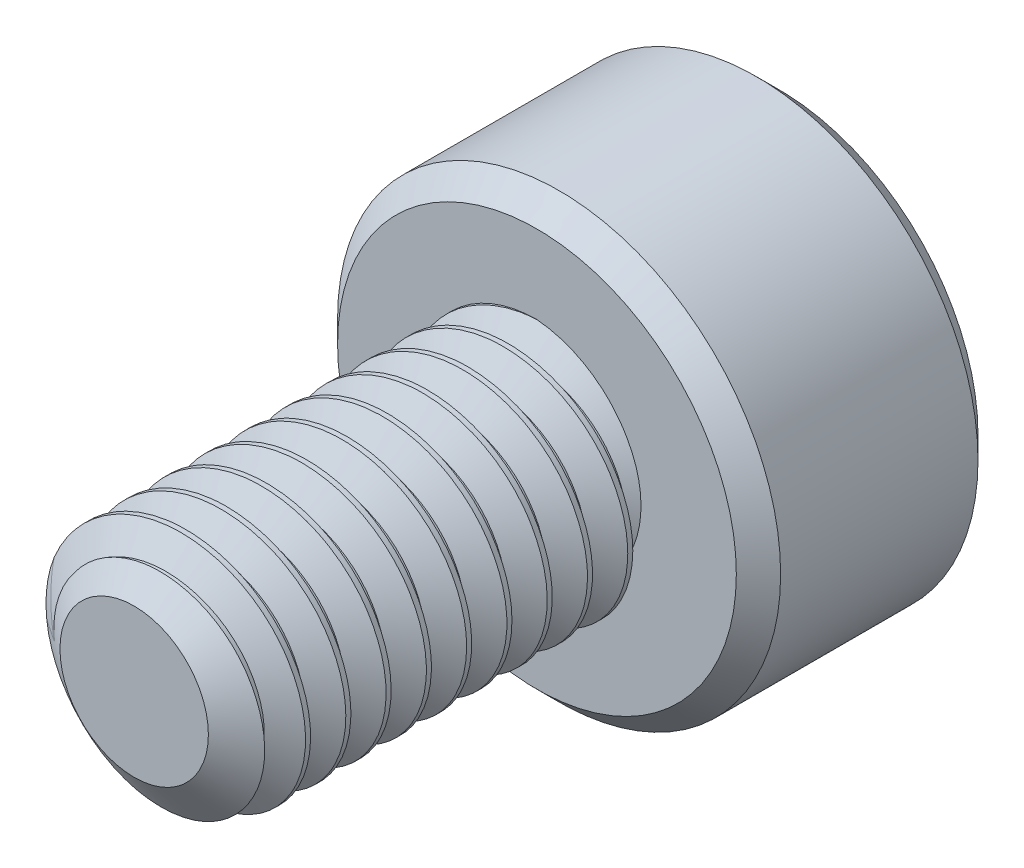
SolidWorks part; units mm, degrees
other "DetailItem1"
ref_plane "Front Plane" through (0, 0, 0) normal (0, 0, 1) x (1, 0, 0)
ref_plane "Top Plane" through (0, 0, 0) normal (0, 1, 0) x (1, 0, 0)
ref_plane "Right Plane" through (0, 0, 0) normal (1, 0, 0) x (0, 0, -1)
sketch "Sketch1" plane through (0, 0, 0) normal (0, 0, 1) x (1, 0, 0)
  circle A0 centre (0, 0) radius 1.5
  dimension "OD" = 3
extrude "Extrude1" add sketch "Sketch1" against normal blind 5
sketch "Sketch2" plane through (0, 0, 0) normal (0, 0, 1) x (1, 0, 0)
  circle A0 centre (0, 0) radius 1.5 construction
  circle A1 centre (0, 0) radius 1.5
curve "Helix/Spiral1" pitch 0.5 height 5.5 radius 1.5 centre (0, 0, 0) axis (0, 0, -1) start towards (0, 1, 0) parameters "pitch"=0.5
sketch "Sketch3" plane through (0, 0, 0) normal (1, 0, 0) x (0, 0, -1)
  line L0 (-0.4375, 1.5) -> (-0.25, 1.1752)
  line L1 (-0.25, 1.1752) -> (-0.1875, 1.1752)
  line L2 (-0.1875, 1.1752) -> (0, 1.5)
  line L3 (-0.4375, 1.5) -> (0, 1.5)
  line L4 (-0.2187, 1.5) -> (-0.2188, 1.1752) construction
  line L5 (-0.3438, 1.3376) -> (-0.0938, 1.3376) construction
  line L6 (0, 1.5) -> (0, -1.5) construction
  dimension "D1" = 0.0625
  dimension "D2" = 0.25
  dimension "D3" = 60
sweep "Cut-Sweep1" cut profiles "Sketch3" path "Helix/Spiral1"
sketch "Sketch4" plane through (0, 0, 0) normal (1, 0, 0) x (0, 0, -1)
  line L0 (0.4053, 1.5) -> (0, 0.9212)
  line L1 (0, 0.9212) -> (0, 1.5)
  line L2 (0.4053, 1.5) -> (0, 1.5)
  line L3 (-0.4375, 1.5) -> (0, 1.5) construction
  line L4 (0, 0) -> (7.0209, 0) construction
  dimension "D1" = 55
  dimension "D2" = 0.254
revolve "Cut-Revolve1" cut sketch "Sketch4" angle 360 about L4
sketch "Sketch6" plane through (0, 0, -5) normal (0, 0, -1) x (-1, 0, 0)
  circle A0 centre (0, 0) radius 2.75
  dimension "head dia" = 5.5
extrude "Extrude2" add sketch "Sketch6" along normal blind 3
sketch "Sketch7" plane through (0, 0, -8) normal (0, 0, -1) x (-1, 0, 0)
  line L1 (0, 1.4434) -> (-1.25, 0.7217)
  line L2 (-1.25, 0.7217) -> (-1.25, -0.7217)
  line L3 (-1.25, -0.7217) -> (0, -1.4434)
  line L4 (0, -1.4434) -> (1.25, -0.7217)
  line L5 (1.25, -0.7217) -> (1.25, 0.7217)
  line L6 (1.25, 0.7217) -> (0, 1.4434)
  circle A0 centre (0, 0) radius 1.25 construction
  dimension "hex dia" = 2.5
extrude "Cut-Extrude1" cut sketch "Sketch7" against normal blind 1.875
sketch "Sketch8" plane through (0, 0, -8) normal (0, 0, -1) x (-1, 0, 0)
  circle A0 centre (0, 0) radius 1.4434
extrude "Cut-Extrude2" cut sketch "Sketch8" against normal through all draft 45
chamfer "Chamfer1" distance 0.275 angle 45 2 edges at (-2.75, 0, -8) (-2.75, 0, -5)
sketch "Sketch10" plane through (0, 0, -5) normal (0, 0, 1) x (1, 0, 0)
  circle A1 centre (0, 0) radius 1.5
  circle A2 centre (0, 0) radius 1.5
  dimension "D1" = 0
ref_plane "Plane1" through (0, 0, 0) normal (0, 0, 1) x (1, 0, 0)
extrude "partial thread" [suppressed] add sketch "Sketch10" along normal up to surface (4 mm away) separate body up to plane "Plane1"
chamfer "Chamfer2" [suppressed] distance 0.06 angle 45
combine bodies "Combine1" [suppressed] operation type add bodies to combine 107 108
sketch "Sketch9" plane through (0, 0, 0) normal (1, 0, 0) x (0, 0, -1)
  line L0 (0, 1.5) -> (0, -1.5) construction
  line L1 (1.25, 1.5) -> (1.25, -1.5) construction
  dimension "D1" = 1.25
ref_point "Point1"
equation "\"D3@Helix/Spiral1\" = \"screw length@Extrude1\"+\"pitch@Helix/Spiral1\""
equation "\"D1@Sketch3\" = \"pitch@Helix/Spiral1\"*.125"
equation "\"D2@Sketch3\" = \"pitch@Helix/Spiral1\"*.5"
equation "\"D1@Cut-Extrude1\" = \"hex dia@Sketch7\"*.75"
equation "\"D1@Chamfer1\" = \"head dia@Sketch6\"*.05"
equation "\"D1@Sketch9\" = \"pitch@Helix/Spiral1\"*2.5"
equation "\"D1@Chamfer2\"=\"OD@Sketch1\"*.02"
